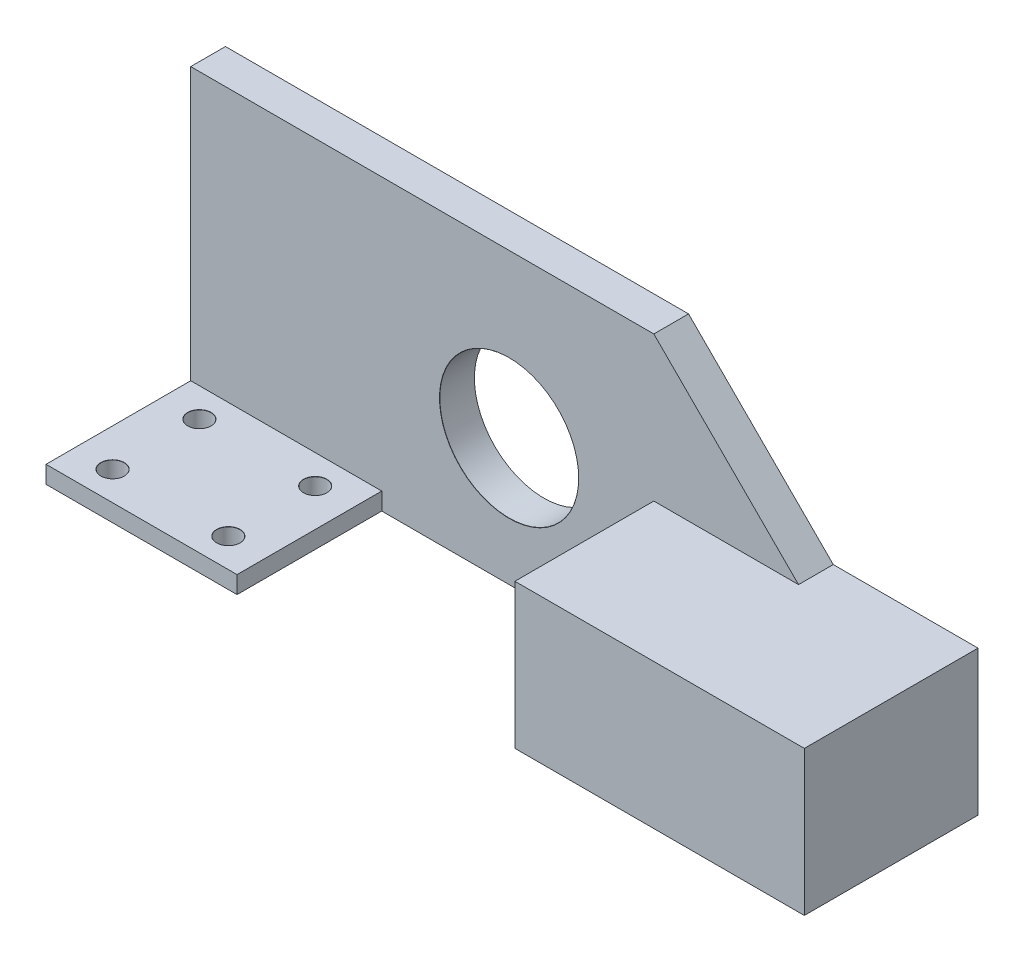
SolidWorks part; units mm, degrees
ref_plane "Front Plane" through (0, 0, 0) normal (0, 0, 1) x (1, 0, 0)
ref_plane "Top Plane" through (0, 0, 0) normal (0, 1, 0) x (1, 0, 0)
ref_plane "Right Plane" through (0, 0, 0) normal (1, 0, 0) x (0, 0, -1)
sketch "Sketch1" plane through (0, 0, 0) normal (0, 0, 1) x (1, 0, 0)
  line L1 (-40, 40) -> (40, 40)
  line L2 (-40, 40) -> (-40, -40)
  line L3 (-40, -40) -> (40, -40)
  line L4 (40, 40) -> (40, -40)
  line L5 (-40, 40) -> (40, -40) construction
  line L6 (-40, -40) -> (40, 40) construction
  point P0 (0, 0)
  dimension "D1" = 80
  dimension "D2" = 80
extrude "Boss-Extrude1" add sketch "Sketch1" along normal mid plane 6
sketch "Sketch2" plane through (0, 0, 3) normal (0, 0, 1) x (1, 0, 0)
  line L1 (-40, -40) -> (-7, -40)
  line L2 (-40, -40) -> (-40, -37)
  line L3 (-40, -37) -> (-7, -37)
  line L4 (-7, -40) -> (-7, -37)
  dimension "D1" = 3
  dimension "D2" = 33
extrude "Boss-Extrude2" add sketch "Sketch2" along normal blind 25
hole_wizard "Ø4.0 (4) Diameter Hole1" positions "Sketch3" profile "Sketch4" hole size "Ø4.0" standard "ANSI Metric"
sketch "Sketch3" plane through (0, -37, 0) normal (0, 1, 0) x (1, 0, 0)
  line L0 (-7, -28) -> (-7, -3) construction
  line L1 (-7, -28) -> (-40, -28) construction
  line L2 (-40, -28) -> (-40, -3) construction
  point P0 (-33.5, -8)
  point P2 (-13.5, -8)
  point P4 (-13.5, -23)
  point P6 (-33.5, -23)
  point P9 (0, 0)
  point P10 (0, 0)
  point P11 (0, 0)
  dimension "D1" = 20
  dimension "D2" = 15
  dimension "D3" = 6.5
  dimension "D4" = 5
  dimension "D5" = 6.5
sketch "Sketch4" plane through (-33.5, -37, 8) normal (1, 0, 0) x (0, 0, 1)
  line L0 (0, 0) -> (0, 9.2017)
  line L1 (0, 9.2017) -> (2, 8)
  line L2 (2, 8) -> (2, 0.025)
  line L3 (2, 0.025) -> (2.025, 0)
  line L5 (2.025, 0) -> (0, 0)
  line L6 (-2, 0.025) -> (-2.025, 0) construction
  line L10 (0, 9.2017) -> (-2, 8) construction
  line L11 (0, -6.35) -> (0, 107.95) construction
  dimension "Hole Dia." = 4
  dimension "Hole Depth" = 8
  dimension "Near C'Sink Dia." = 4.05
  dimension "Near C'Sink Angle" = 90
  dimension "Drill Angle" = 118
hole_wizard "Ø24.0 (24) Diameter Hole1" positions "Sketch7" profile "Sketch8" hole size "Ø24.0" standard "ANSI Metric"
sketch "Sketch7" plane through (0, 0, 3) normal (0, 0, 1) x (1, 0, 0)
  line L0 (-7, -40) -> (40, -40) construction
  line L1 (40, -40) -> (40, 40) construction
  point P0 (15, -18.07)
  dimension "D1" = 21.93
  dimension "D2" = 25
sketch "Sketch8" plane through (15, -18.07, 3) normal (1, 0, 0) x (0, -1, 0)
  line L0 (0, 0) -> (0, 15.2103)
  line L1 (0, 15.2103) -> (12, 8)
  line L2 (12, 8) -> (12, 0.025)
  line L3 (12, 0.025) -> (12.025, 0)
  line L5 (12.025, 0) -> (0, 0)
  line L6 (-12, 0.025) -> (-12.025, 0) construction
  line L10 (0, 15.2103) -> (-12, 8) construction
  line L11 (0, -6.35) -> (0, 107.95) construction
  dimension "Hole Dia." = 24
  dimension "Hole Depth" = 8
  dimension "Near C'Sink Dia." = 24.05
  dimension "Near C'Sink Angle" = 90
  dimension "Drill Angle" = 118
sketch "Sketch9" plane through (0, 0, 3) normal (0, 0, 1) x (1, 0, 0)
  line L0 (40, -40) -> (40, 40) construction
  line L1 (-40, 40) -> (40, 40)
  line L2 (-40, 40) -> (-40, 10)
  line L3 (-40, 10) -> (40, 10)
  line L4 (40, 40) -> (40, 10)
  dimension "D1" = 80
  dimension "D2" = 30
extrude "Cut-Extrude1" cut sketch "Sketch9" against normal blind 15
sketch "Sketch10" plane through (0, 0, -3) normal (0, 0, -1) x (-1, 0, 0)
  line L1 (-40, -15) -> (-90, -15)
  line L2 (-40, -15) -> (-40, -40)
  line L3 (-40, -40) -> (-90, -40)
  line L4 (-90, -15) -> (-90, -40)
  point P5 (0, 0)
  dimension "D1" = 50
  dimension "D2" = 25
extrude "Boss-Extrude4" add sketch "Sketch10" against normal blind 30
chamfer "Chamfer2" distance 25 angle 45 1 edges at (40, -15, 0)
